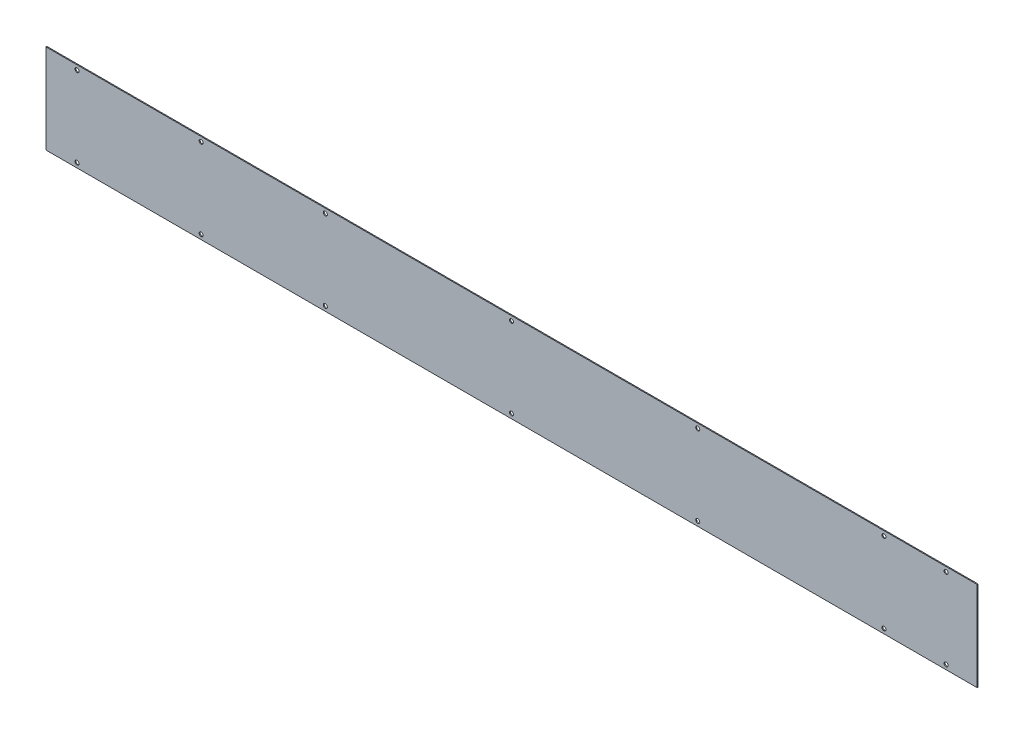
SolidWorks part; units mm, degrees
ref_plane "Front Plane" through (0, 0, 0) normal (0, 0, 1) x (1, 0, 0)
ref_plane "Top Plane" through (0, 0, 0) normal (0, 1, 0) x (1, 0, 0)
ref_plane "Right Plane" through (0, 0, 0) normal (1, 0, 0) x (0, 0, -1)
sketch "Sketch2" plane through (0, 0, 0) normal (0, 0, 1) x (1, 0, 0)
  line L1 (-381, -36.576) -> (381, -36.576)
  line L2 (-381, -36.576) -> (-381, 36.576)
  line L3 (-381, 36.576) -> (381, 36.576)
  line L4 (381, -36.576) -> (381, 36.576)
  line L5 (-381, -36.576) -> (381, 36.576) construction
  line L6 (-381, 36.576) -> (381, -36.576) construction
  point P0 (0, 0)
  point P6 (0, 36.576)
  dimension "D1" = 762
  dimension "D2" = 73.152
base flange "Base-Flange1" sketch "Sketch2" thickness 0.7595 reverse thickness direction no parameters "D1"=0.7366
sketch "Sketch13" plane through (0, 0, 0) normal (0, 0, 1) x (1, 0, 0)
  line L0 (381, 36.576) -> (-381, 36.576) construction
  line L1 (-381, -36.576) -> (381, -36.576) construction
  line L2 (-381, 36.576) -> (-381, -36.576) construction
  circle A1 centre (-254, 32.766) radius 1.651
  circle A2 centre (-254, -32.766) radius 1.651
  circle A3 centre (0, 32.766) radius 1.651
  circle A4 centre (304.8, 32.766) radius 1.651
  circle A5 centre (304.8, -32.766) radius 1.651
  circle A6 centre (0, -32.766) radius 1.651
  circle A7 centre (355.6, 32.766) radius 1.651
  circle A8 centre (355.6, -32.766) radius 1.651
  circle A9 centre (152.4, 32.766) radius 1.651
  circle A10 centre (152.4, -32.766) radius 1.651
  circle A11 centre (-152.4, 32.766) radius 1.651
  circle A12 centre (-152.4, -32.766) radius 1.651
  circle A13 centre (-355.6, 32.766) radius 1.651
  circle A14 centre (-355.6, -32.766) radius 1.651
  dimension "D1" = 3.302
  dimension "D2" = 3.81
  dimension "D3" = 3.81
  dimension "D4" = 254
  dimension "D5" = 127
  dimension "D6" = 50.8
  dimension "D7" = 304.8
  dimension "D8" = 152.4
  dimension "D9" = 101.6
  dimension "D10" = 101.6
extrude "Cut-Extrude1" cut sketch "Sketch13" against normal through all normal cut yes
sketch "Bend-Lines1" [suppressed] plane through (0, 0, 0) normal (0, 1, 0) x (1, 0, 0)
sketch "Bounding-Box1" [suppressed] plane through (0, 0, 0) normal (0, 1, 0) x (1, 0, 0)
sheet metal parameters "Sheet-Metal1" thickness 0.7595 parameters "D1"=0.7366
flat pattern "Flat-Pattern1" [suppressed]
sketch "Bend-Lines2" plane through (0, 0, 0) normal (0, 1, 0) x (1, 0, 0)
sketch3d "Bounding-Box2" [suppressed]
  line L0 (-571.5, -36.576, 0) -> (571.5, -36.576, 0) construction
  line L1 (-571.5, 36.576, 0) -> (571.5, 36.576, 0) construction
  line L2 (-571.5, -36.576, 0) -> (-571.5, 36.576, 0) construction
  line L3 (571.5, -36.576, 0) -> (571.5, 36.576, 0) construction
sheet metal parameters "Sheet-Metal4" thickness 0.7595 parameters "D1"=0.7366
flat pattern "Flat-Pattern1"
sketch "Bend-Lines2" plane through (0, 0, 0) normal (0, 1, 0) x (1, 0, 0)
sketch3d "Bounding-Box2" [suppressed]
  line L0 (-381, -36.576, 0) -> (381, -36.576, 0) construction
  line L1 (-381, 36.576, 0) -> (381, 36.576, 0) construction
  line L2 (-381, -36.576, 0) -> (-381, 36.576, 0) construction
  line L3 (381, -36.576, 0) -> (381, 36.576, 0) construction
